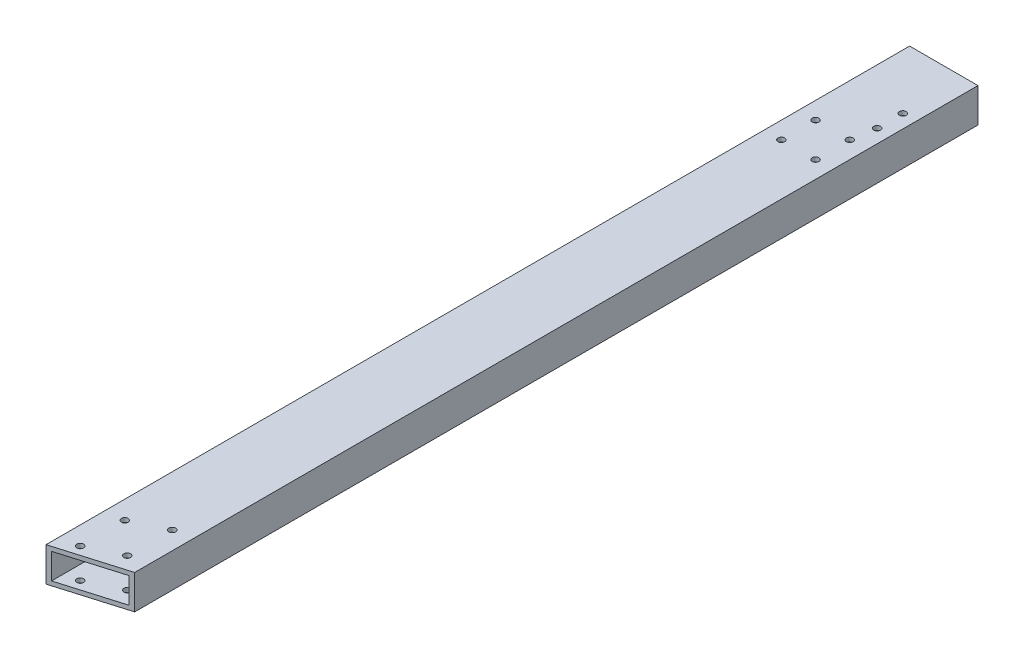
SolidWorks part; units mm, degrees
material "1060 Alloy"
ref_plane "Front Plane" through (0, 0, 0) normal (0, 0, 1) x (1, 0, 0)
ref_plane "Top Plane" through (0, 0, 0) normal (0, 1, 0) x (1, 0, 0)
ref_plane "Right Plane" through (0, 0, 0) normal (1, 0, 0) x (0, 0, -1)
sketch "Sketch1" plane through (0, 0, 0) normal (0, 0, 1) x (1, 0, 0)
  line L0 (-22.225, 9.525) -> (22.225, 9.525)
  line L2 (-25.4, 12.7) -> (25.4, 12.7)
  line L3 (-25.4, 12.7) -> (-25.4, -12.7)
  line L4 (-25.4, -12.7) -> (25.4, -12.7)
  line L5 (25.4, 12.7) -> (25.4, -12.7)
  line L10 (22.225, 9.525) -> (22.225, -9.525)
  line L11 (-22.225, -9.525) -> (22.225, -9.525)
  line L12 (-22.225, 9.525) -> (-22.225, -9.525)
  point P12 (0, 12.7)
  point P14 (25.4, 0)
  dimension "Wall Thickness" = 3.175
  dimension "Outside Width" = 50.8
  dimension "Outside Height" = 25.4
  dimension "Inside Height" = 19.05
  dimension "Inside Width" = 44.45
sketch "Sketch2" plane through (0, 0, 0) normal (1, 0, 0) x (0, 0, -1)
  line L0 (320.675, 0) -> (-320.675, 0)
  point P4 (0, 0)
  point P7 (-320.675, 0)
  point P10 (320.675, 0)
  dimension "Length" = 641.35
sketch "Sketch3" plane through (0, 0, 0) normal (0, 0, 1) x (1, 0, 0)
  line L21 (25.4, 12.7) -> (-25.4, 12.7)
  line L22 (25.4, -12.7) -> (25.4, 12.7)
  line L23 (-25.4, -12.7) -> (25.4, -12.7)
  line L24 (-25.4, 12.7) -> (-25.4, -12.7)
  line L25 (25.4, 12.7) -> (-25.4, 12.7)
  line L26 (25.4, -12.7) -> (25.4, 12.7)
  line L27 (-25.4, -12.7) -> (25.4, -12.7)
  line L28 (-25.4, 12.7) -> (-25.4, -12.7)
  line L29 (22.225, 9.525) -> (-22.225, 9.525)
  line L30 (22.225, -9.525) -> (22.225, 9.525)
  line L31 (-22.225, -9.525) -> (22.225, -9.525)
  line L32 (-22.225, 9.525) -> (-22.225, -9.525)
  line L33 (22.225, 9.525) -> (-22.225, 9.525)
  line L34 (22.225, -9.525) -> (22.225, 9.525)
  line L35 (-22.225, -9.525) -> (22.225, -9.525)
  line L36 (-22.225, 9.525) -> (-22.225, -9.525)
  dimension "D1" = 0
  dimension "D2" = 0
extrude "Boss-Extrude1" add sketch "Sketch3" along normal up to vertex (320.675 mm away) and the other way up to vertex (320.675 mm away) up to point (0, 0, 320.675) other way up to point (0, 0, -320.675)
sketch "Drawing Reference" plane through (0, 0, 0) normal (1, 0, 0) x (0, 0, -1)
  line L0 (-320.675, 0) -> (320.675, 0) construction
  line L1 (0, -12.7) -> (0, 12.7) construction
  line L2 (-320.675, -12.7) -> (320.675, -12.7) construction
  line L5 (-320.675, 12.7) -> (320.675, 12.7) construction
  point P7 (-284.099, 0)
  point P8 (284.099, 0)
  dimension "D1" = 36.576
sketch "Sketch4" plane through (0, 12.7, 0) normal (0, 1, 0) x (1, 0, 0)
  line L0 (-25.4, -320.675) -> (25.4, -305.6274)
  line L1 (25.4, -320.675) -> (25.4, 320.675) construction
  line L2 (25.4, -320.675) -> (-25.4, -320.675)
  dimension "D1" = 16.5
extrude "Cut-Extrude1" cut sketch "Sketch4" against normal through all and the other way through all flip side to cut
sketch "Sketch6" plane through (0, -12.7, 0) normal (0, -1, 0) x (1, 0, 0)
  line L0 (25.4, 305.6274) -> (22.1108, 294.5233) construction
  line L1 (25.4, 279.2824) -> (22.225, 279.2824) construction
  line L2 (25.4, 305.6274) -> (25.4, -320.675) construction
  line L3 (22.225, 279.2824) -> (22.225, 313.1512) construction
  line L4 (22.1108, 294.5233) -> (11.811, 297.5742) construction
  line L5 (-11.811, 250.3501) -> (-11.811, 328.3651) construction
  line L6 (-25.4, 320.675) -> (-27.5213, 313.5136) construction
  line L7 (-25.4, 287.6223) -> (-22.225, 287.6223) construction
  line L8 (-25.4, 320.675) -> (-25.4, -320.675) construction
  line L9 (-22.225, 287.6223) -> (-22.225, 328.3651) construction
  line L10 (-27.5213, 313.5136) -> (-11.811, 308.86) construction
  line L11 (11.811, 250.3501) -> (11.811, 313.1512) construction
  line L12 (-27.5213, 313.5136) -> (-36.5388, 283.071) construction
  line L13 (22.1108, 294.5233) -> (13.0933, 264.0807) construction
  line L14 (-37.6746, 250.3501) -> (48.6057, 250.3501) construction
  line L15 (-11.811, 287.6223) -> (-11.811, 328.3651) construction
  line L16 (11.811, 279.2824) -> (11.811, 313.1512) construction
  line L17 (-36.5388, 283.071) -> (-11.811, 275.7463) construction
  line L18 (13.0933, 264.0807) -> (11.811, 264.4606) construction
  line L19 (-11.811, 308.86) -> (11.811, 264.4606) construction
  line L20 (11.811, 297.5742) -> (-11.811, 275.7463) construction
  point P10 (0, 286.6603)
  dimension "D1" = 10.414
  dimension "D2" = 10.414
hole_wizard "#10 Clearance Hole1" positions "Sketch9" profile "Sketch10" hole size "#10" standard "ANSI Inch"
sketch "Sketch9" plane through (0, 12.7, 0) normal (0, 1, 0) x (1, 0, 0)
  line L0 (13.0933, -264.0807) -> (11.811, -264.4606) construction
  point P0 (-11.811, -275.7463)
  point P3 (-11.811, -308.86)
  point P6 (11.811, -297.5742)
  point P9 (12.0472, -264.3906)
sketch "Sketch10" plane through (-11.811, 12.7, 275.7463) normal (1, 0, 0) x (0, 0, 1)
  line L0 (0, 0) -> (0, 31.9757)
  line L1 (0, 31.9757) -> (2.4892, 30.48)
  line L2 (2.4892, 30.48) -> (2.4892, 0)
  line L5 (2.4892, 0) -> (0, 0)
  line L10 (0, 31.9757) -> (-2.4892, 30.48) construction
  line L11 (0, -6.35) -> (0, 107.95) construction
  dimension "Hole Dia." = 4.9784
  dimension "Hole Depth" = 30.48
  dimension "Drill Angle" = 118
sketch "Sketch12" plane through (0, -12.7, 0) normal (0, -1, 0) x (1, 0, 0)
  line L0 (13.0291, -316.23) -> (10.4891, -316.23) construction
  line L1 (-9.8309, -316.23) -> (-12.3709, -316.23) construction
  line L2 (13.0291, -299.72) -> (10.4891, -299.72) construction
  line L3 (-9.8309, -299.72) -> (-12.3709, -299.72) construction
hole_wizard "#10 Clearance Hole3" positions "Sketch15" profile "Sketch16" hole size "#10" standard "ANSI Inch"
sketch "Sketch15" plane through (0, -12.7, 0) normal (0, -1, 0) x (-1, 0, 0)
  point P0 (-13.0291, 299.72)
  point P3 (12.3709, 299.72)
  point P6 (12.3709, 316.23)
  point P9 (-13.0291, 316.23)
sketch "Sketch16" plane through (13.0291, -12.7, -299.72) normal (1, 0, 0) x (0, 0, -1)
  line L0 (0, 0) -> (0, 6.5757)
  line L1 (0, 6.5757) -> (2.4892, 5.08)
  line L2 (2.4892, 5.08) -> (2.4892, 0)
  line L5 (2.4892, 0) -> (0, 0)
  line L10 (0, 6.5757) -> (-2.4892, 5.08) construction
  line L11 (0, -6.35) -> (0, 107.95) construction
  dimension "Hole Dia." = 4.9784
  dimension "Hole Depth" = 5.08
  dimension "Drill Angle" = 118
sketch "Sketch17" plane through (0, -12.7, 0) normal (0, -1, 0) x (1, 0, 0)
  line L0 (12.7, -238.125) -> (-12.7, -238.125) construction
  line L1 (-12.7, -238.125) -> (-12.7, -212.725) construction
  line L2 (-12.7, -212.725) -> (12.7, -212.725) construction
  line L3 (12.7, -212.725) -> (12.7, -238.125) construction
hole_wizard "#10 Clearance Hole4" positions "Sketch18" profile "Sketch19" hole size "#10" standard "ANSI Inch" end condition through all
sketch "Sketch18" plane through (0, -12.7, 0) normal (0, -1, 0) x (-1, 0, 0)
  point P0 (-12.7, 238.125)
  point P3 (12.7, 238.125)
  point P6 (12.7, 212.725)
  point P14 (-12.7, 212.725)
  point P18 (-15.4075, 274.8363)
  point P21 (-15.4075, 255.7863)
sketch "Sketch19" plane through (12.7, -12.7, -238.125) normal (1, 0, 0) x (0, 0, -1)
  line L0 (0, 0) -> (0, 25.4)
  line L1 (0, 25.4) -> (2.4892, 25.4)
  line L2 (2.4892, 25.4) -> (2.4892, 0)
  line L5 (2.4892, 0) -> (0, 0)
  line L11 (0, -6.35) -> (0, 107.95) construction
  dimension "Thru Hole Dia." = 4.9784
  dimension "Thru Hole Depth" = 25.4
equation "\"D1@Drawing Reference\"=\"Outside Width@Sketch1\" * 0.72"
